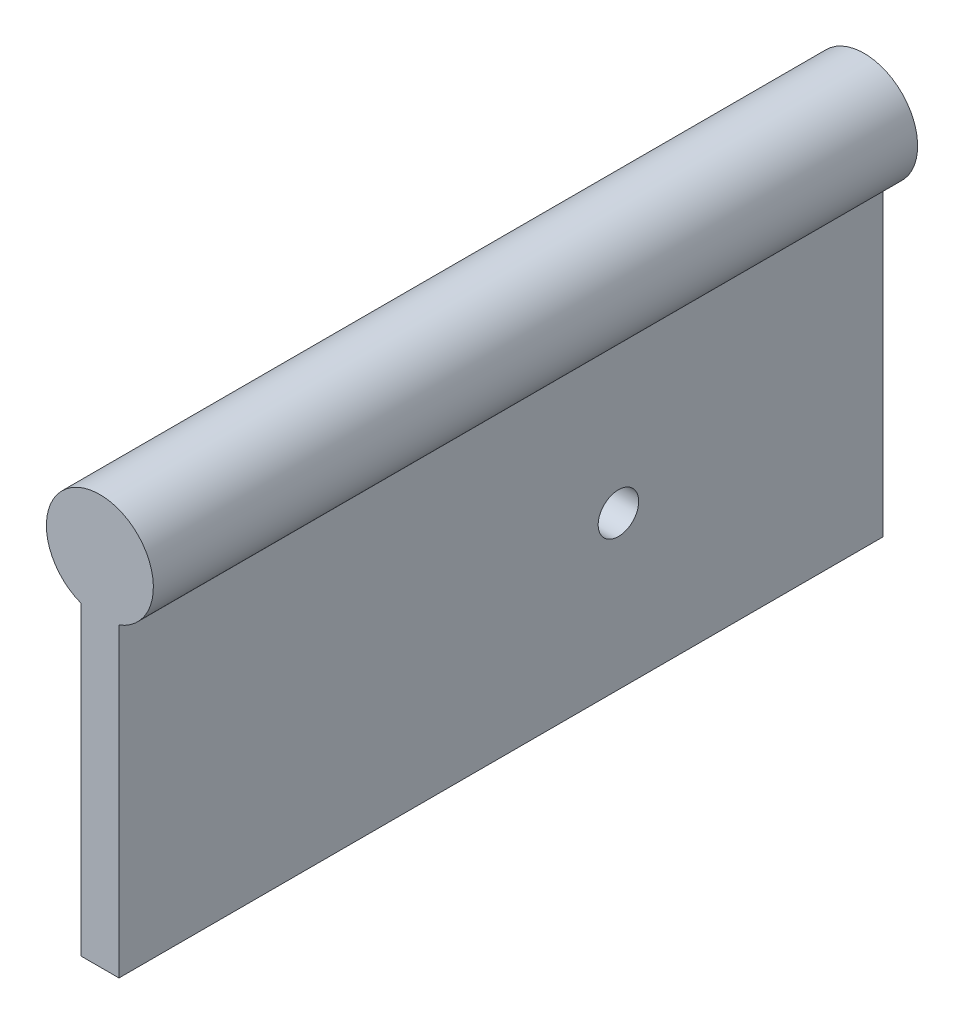
SolidWorks part; units mm, degrees
ref_plane "Front Plane" through (0, 0, 0) normal (1, 0, 0) x (0, 1, 0)
ref_plane "Top Plane" through (0, 0, 0) normal (0, 0, 1) x (0, 1, 0)
ref_plane "Right Plane" through (0, 0, 0) normal (0, 1, 0) x (-1, 0, 0)
sketch "Sketch1" plane through (0, 0, 0) normal (1, 0, 0) x (0, 1, 0)
  line L0 (-20, 0) -> (20, 0) construction
  line L1 (-20, 50) -> (20, 50)
  line L2 (-20, 50) -> (-20, -50)
  line L3 (-20, -50) -> (20, -50)
  line L4 (20, 50) -> (20, -50)
  line L5 (-20, 50) -> (20, -50) construction
  line L6 (-20, -50) -> (20, 50) construction
  circle A0 centre (0, 15.35) radius 4.8
  circle A1 centre (0, -15.35) radius 4.8
  point P0 (0, 0)
  dimension "D3" = 9.6
  dimension "D1" = 40
  dimension "D2" = 100
  dimension "D4" = 30.7
extrude "Boss-Extrude1" add sketch "Sketch1" along normal blind 5 contours A0 | A1 | L4 L1 L2 L3 A1 A0 region at (0, 0, 0) region at (0, 0, 15.35) region at (0, 0, -15.35)
extrude "Boss-Extrude2" add sketch "Sketch1<3>" against normal blind 5.2 contours A0 | A1
sketch "Sketch1<3>" plane through (0, 0, 0) normal (1, 0, 0) x (0, 1, 0) same geometry as "Sketch1"
sketch "Sketch2" plane through (-5.2, 0, 0) normal (-1, 0, 0) x (0, -1, 0)
  circle A0 centre (0, -15.35) radius 2.5
  dimension "D1" = 5
extrude "Cut-Extrude1" cut sketch "Sketch2" against normal through all
sketch "Sketch3" plane through (5, 0, 0) normal (1, 0, 0) x (0, 0, -1)
  circle A0 centre (15.35, 0) radius 2.65
  dimension "D1" = 5.3
extrude "Cut-Extrude2" cut sketch "Sketch3" against normal up to surface (5 mm away) up to face at (0, 0, 10.55)
chamfer "Chamfer1" distance 0.15 angle 45 1 edges at (0, 0, -17.85)
sketch "Sketch4" plane through (0, 0, -50) normal (0, 0, -1) x (1, 0, 0)
  line L0 (5, 20) -> (5, -20) construction
  line L2 (5, -20) -> (0, -20)
  arc A1 (0, -20) -> (5, -20) centre (2.5, -26.5383) ccw
  dimension "D2" = 7
extrude "Boss-Extrude3" add sketch "Sketch4" against normal up to surface (100 mm away) up to face at (2.5, 0, 50)
